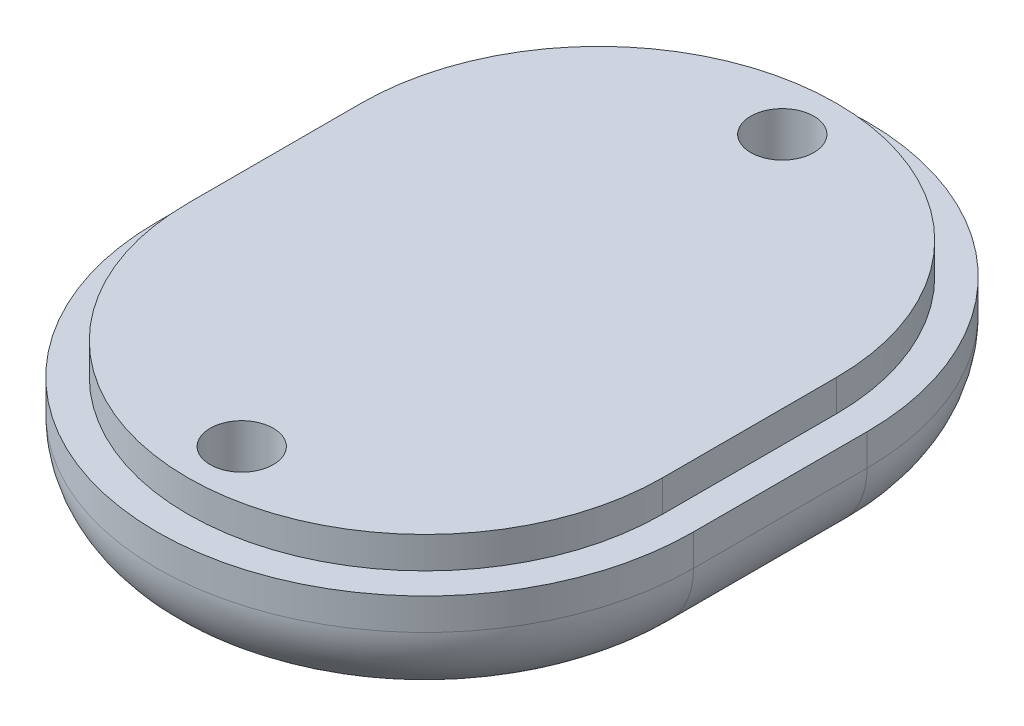
SolidWorks part; units mm, degrees
ref_plane "Front Plane" through (0, 0, 0) normal (0, 0, 1) x (1, 0, 0)
ref_plane "Top Plane" through (0, 0, 0) normal (0, 1, 0) x (1, 0, 0)
ref_plane "Right Plane" through (0, 0, 0) normal (1, 0, 0) x (0, 0, -1)
sketch "Sketch1" plane through (0, 0, 0) normal (0, 1, 0) x (1, 0, 0)
  line L6 (15.05, -21.5) -> (15.05, -10.5)
  line L7 (-15.05, -10.5) -> (-15.05, -21.5)
  line L8 (15.05, -21.5) -> (15.05, -10.5)
  line L9 (-15.05, -10.5) -> (-15.05, -21.5)
  circle A1 centre (0, -33.1242) radius 2 construction
  circle A2 centre (0, 1.1242) radius 2
  circle A3 centre (0, -33.1242) radius 2
  circle A5 centre (0, 1.1242) radius 2 construction
  arc A14 (15.05, -10.5) -> (-15.05, -10.5) centre (0, -10.5) ccw
  arc A15 (-15.05, -21.5) -> (15.05, -21.5) centre (0, -21.5) ccw
  arc A16 (15.05, -10.5) -> (-15.05, -10.5) centre (0, -10.5) ccw
  arc A17 (-15.05, -21.5) -> (15.05, -21.5) centre (0, -21.5) ccw
  dimension "D1" = 0.15
extrude "Boss-Extrude1" add sketch "Sketch1" along normal blind 2
sketch "Sketch2" plane through (0, 0, 0) normal (0, -1, 0) x (1, 0, 0)
  line L6 (17, 10.5) -> (17, 21.5)
  line L7 (-17, 21.5) -> (-17, 10.5)
  line L8 (17, 10.5) -> (17, 21.5)
  line L9 (-17, 21.5) -> (-17, 10.5)
  arc A8 (-17, 10.5) -> (17, 10.5) centre (0, 10.5) ccw
  arc A9 (17, 21.5) -> (-17, 21.5) centre (0, 21.5) ccw
  arc A10 (-17, 10.5) -> (17, 10.5) centre (0, 10.5) ccw
  arc A11 (17, 21.5) -> (-17, 21.5) centre (0, 21.5) ccw
  dimension "D2" = 34
  dimension "D1" = 1.95
extrude "Boss-Extrude2" add sketch "Sketch2" along normal blind 2
sketch "Sketch3" plane through (0, -2, 0) normal (0, -1, 0) x (1, 0, 0)
  line L0 (-17, 21.5) -> (-17, 10.5)
  line L1 (17, 10.5) -> (17, 21.5) construction
  line L2 (17, 21.5) -> (17, 10.5)
  line L3 (-17, 21.5) -> (-17, 10.5) construction
  arc A0 (17, 21.5) -> (-17, 21.5) centre (0, 21.5) ccw
  arc A1 (-17, 10.5) -> (17, 10.5) centre (0, 10.5) ccw
  arc A2 (17, 21.5) -> (-17, 21.5) centre (0, 21.5) ccw construction
  arc A3 (-17, 10.5) -> (17, 10.5) centre (0, 10.5) ccw construction
extrude "Boss-Extrude3" add sketch "Sketch3" along normal blind 5 separate body
sketch "Sketch5" plane through (0, -2, 0) normal (0, -1, 0) x (1, 0, 0)
  circle A0 centre (0, 33.1242) radius 3.3
  circle A1 centre (0, -1.1242) radius 3.3
  circle A2 centre (0, 33.1242) radius 2 construction
  circle A3 centre (0, -1.1242) radius 2 construction
  dimension "D1" = 6.6
fillet "Fillet2" radius 5 4 edges at (17, -7, 16) (-17, -7, 16) (0, -7, -6.5) (0, -7, 38.5)
sketch "Sketch4" plane through (0, 0, 0) normal (0, 1, 0) x (1, 0, 0)
  circle A0 centre (0, 1.1242) radius 2
  circle A1 centre (0, -33.1242) radius 2
  circle A2 centre (0, -33.1242) radius 2 construction
  circle A3 centre (0, 1.1242) radius 2 construction
extrude "Cut-Extrude1" cut sketch "Sketch4" against normal blind 7
extrude "Cut-Extrude2" cut sketch "Sketch5" along normal blind 5
